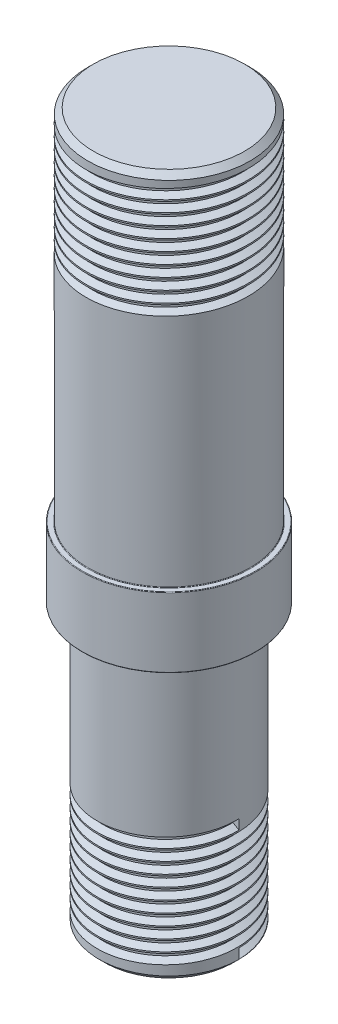
SolidWorks part; units mm, degrees
ref_plane "Płaszczyzna przednia" through (0, 0, 0) normal (0, 0, 1) x (1, 0, 0)
ref_plane "Płaszczyzna górna" through (0, 0, 0) normal (0, 1, 0) x (1, 0, 0)
ref_plane "Płaszczyzna prawa" through (0, 0, 0) normal (1, 0, 0) x (0, 0, -1)
sketch "Szkic1" plane through (0, 0, 0) normal (0, 0, 1) x (1, 0, 0)
  line L0 (0, 0) -> (0, 126.5) construction
  line L1 (0, 0) -> (11.5, 0)
  line L2 (12.5, 1) -> (12.5, 49.9)
  line L3 (12.6, 50) -> (15.4, 50)
  line L4 (15.5, 50.1) -> (15.5, 62.4)
  line L5 (15.4, 62.5) -> (14.6, 62.5)
  line L6 (14.5, 62.6) -> (14.5, 125.5)
  line L7 (13.5, 126.5) -> (0, 126.5)
  line L8 (14.5, 125.5) -> (13.5, 126.5)
  line L9 (11.5, 0) -> (12.5, 1)
  line L10 (0, 0) -> (0, 126.5)
  arc A0 (15.4, 50) -> (15.5, 50.1) centre (15.4, 50.1) ccw
  arc A1 (15.5, 62.4) -> (15.4, 62.5) centre (15.4, 62.4) ccw
  arc A2 (14.5, 62.6) -> (14.6, 62.5) centre (14.6, 62.6) ccw
  arc A3 (12.5, 49.9) -> (12.6, 50) centre (12.6, 49.9) cw
  point P5 (12.5, 0)
  point P10 (14.5, 126.5)
  point P16 (15.5, 50)
  point P19 (15.5, 62.5)
  point P22 (14.5, 62.5)
  point P25 (12.5, 50)
  dimension "D8" = 0.1
  dimension "D1" = 12.5
  dimension "D2" = 50
  dimension "D3" = 3
  dimension "D4" = 12.5
  dimension "D5" = 1
  dimension "D6" = 64
  dimension "D7" = 14.5
revolve "Obrót1" add sketch "Szkic1" angle 360 about L0
thread "Gwint1" pitch 2 method cut profile "Profil gwintu1" start angle 0, offset 0, length 20, pitch 2, diameter 29
ref_plane "Płaszczyzna4" through (-14.5, 125.5, 0) normal (0, 0, 1) x (-1, 0, 0)
sketch "Profil gwintu1" plane through (-14.5, 125.5, 0) normal (0, 0, 1) x (-1, 0, 0)
  line L0 (0, 0) -> (0, 2) construction
  line L11 (0, 0) -> (0, 1.75)
  line L12 (0, 1.75) -> (-1.0825, 1.125)
  line L13 (-1.0825, 1.125) -> (-1.0825, 0.625)
  line L15 (-1.0825, 0.625) -> (0, 0)
  line L17 (-1.0825, 0.875) -> (0, 0.875) construction
  point P2 (0, 0)
  dimension "Pitch" = 2
  dimension "Profile_Angle" = 60
  dimension "Profile_Land" = 0.5
  dimension "Profile_Height" = 1.0825
thread "Gwint2" pitch 2 method cut profile "Profil gwintu2" start angle 0, offset 0, length 20, pitch 2, diameter 25
ref_plane "Płaszczyzna5" through (12.5, 1, 0) normal (0, 0, 1) x (1, 0, 0)
sketch "Profil gwintu2" plane through (12.5, 1, 0) normal (0, 0, 1) x (1, 0, 0)
  line L0 (0, 0) -> (0, 2) construction
  line L11 (0, 0) -> (0, 1.75)
  line L12 (0, 1.75) -> (-1.0825, 1.125)
  line L13 (-1.0825, 1.125) -> (-1.0825, 0.625)
  line L15 (-1.0825, 0.625) -> (0, 0)
  line L17 (-1.0825, 0.875) -> (0, 0.875) construction
  point P2 (0, 0)
  dimension "Pitch" = 2
  dimension "Profile_Angle" = 60
  dimension "Profile_Land" = 0.5
  dimension "Profile_Height" = 1.0825
